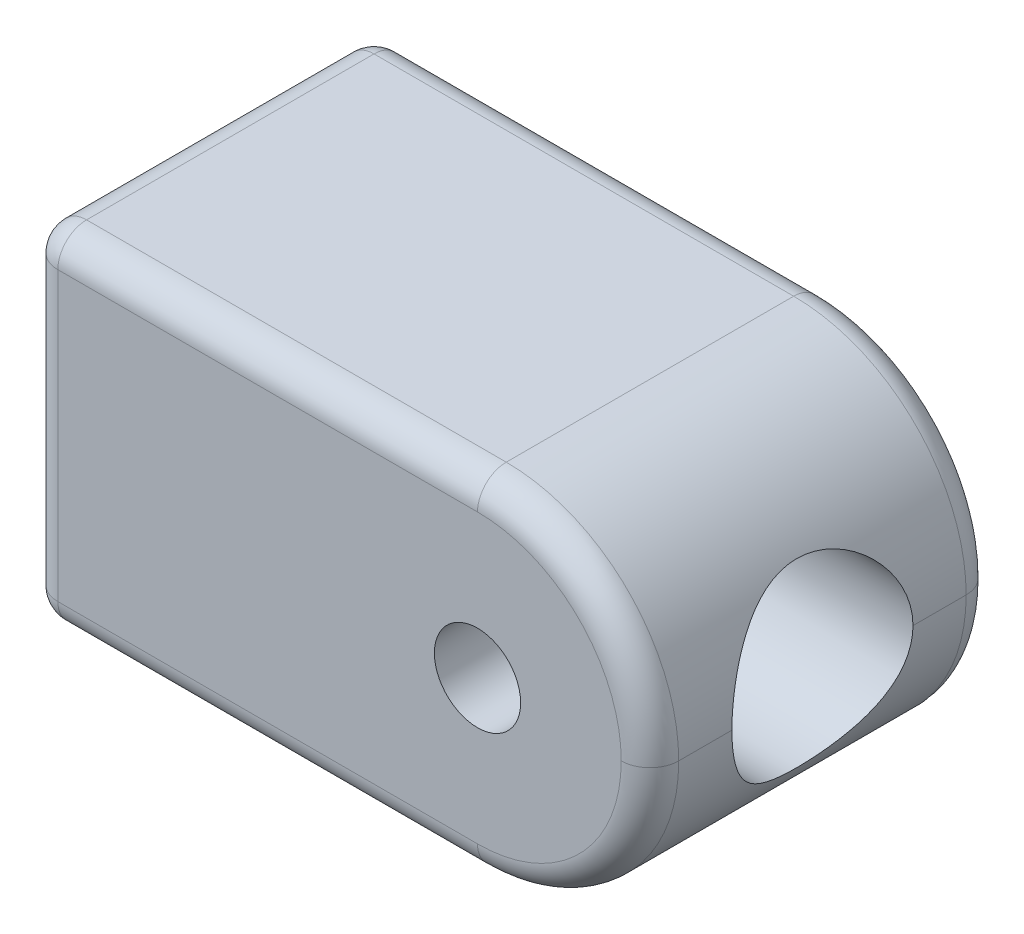
SolidWorks part; units mm, degrees
material "6061 Alloy"
ref_plane "Front Plane" through (0, 0, 0) normal (0, 0, 1) x (1, 0, 0)
ref_plane "Top Plane" through (0, 0, 0) normal (0, 1, 0) x (1, 0, 0)
ref_plane "Right Plane" through (0, 0, 0) normal (1, 0, 0) x (0, 0, -1)
sketch "Sketch1" plane through (0, 0, 0) normal (0, 0, 1) x (1, 0, 0)
  line L1 (12.7, 12.7) -> (-33.02, 12.7)
  line L2 (12.7, 12.7) -> (12.7, -12.7)
  line L3 (12.7, -12.7) -> (-33.02, -12.7)
  line L4 (-33.02, 12.7) -> (-33.02, -12.7)
  circle A0 centre (0, 0) radius 12.7 construction
  circle A1 centre (0, 0) radius 3.175
  dimension "D1" = 25.4
  dimension "D3" = 6.35
  dimension "D2" = 45.72
extrude "Boss-Extrude1" add sketch "Sketch1" along normal blind 25.4
sketch "Sketch3" plane through (0, 0, 25.4) normal (0, 0, 1) x (1, 0, 0)
  line L0 (12.7, 0) -> (-3.175, 0) construction
  line L1 (-3.175, 0) -> (-7.5406, 0) construction
  line L2 (12.7, -12.7) -> (12.7, 12.7) construction
  circle A0 centre (0, 0) radius 3.175 construction
  point P10 (12.7, 0)
  dimension "D1" = 4.3656
sketch "Sketch2" plane through (12.7, 0, 0) normal (1, 0, 0) x (0, 0, -1)
  line L1 (-25.4, 12.7) -> (0, 12.7) construction
  line L2 (-25.4, 12.7) -> (-25.4, -12.7) construction
  line L3 (-25.4, -12.7) -> (0, -12.7) construction
  line L4 (0, 12.7) -> (0, -12.7) construction
  line L5 (-25.4, 12.7) -> (0, -12.7) construction
  line L6 (-25.4, -12.7) -> (0, 12.7) construction
  circle A0 centre (-12.7, 0) radius 6.6675
  circle A1 centre (-12.7, 0) radius 3.175
  point P4 (-12.7, 0)
  dimension "D1" = 6.35
  dimension "D2" = 13.335
extrude "Cut-Extrude1" cut sketch "Sketch2" against normal blind 20.2406 contours A1 | A0 A1 region at (12.7, 0, 19.1789) region at (12.7, 0, 12.7)
extrude "Cut-Extrude2" cut sketch "Sketch2<4>" against normal through all contours A1 region at (12.7, 0, 12.7)
sketch "Sketch2<4>" plane through (12.7, 0, 0) normal (1, 0, 0) x (0, 0, -1) same geometry as "Sketch2"
fillet "Fillet1" radius 12.7 2 edges at (12.7, -12.7, 12.7) (12.7, 12.7, 12.7)
fillet "Fillet2" radius 2.1167 12 edges at (-16.51, -12.7, 0) (8.9803, -8.9803, 0) (8.9803, 8.9803, 0) (-16.51, -12.7, 25.4) (8.9803, -8.9803, 25.4) (8.9803, 8.9803, 25.4) (-33.02, -12.7, 12.7) (-33.02, 12.7, 12.7) (-33.02, 0, 0) (-33.02, 0, 25.4) (-16.51, 12.7, 0) (-16.51, 12.7, 25.4)
